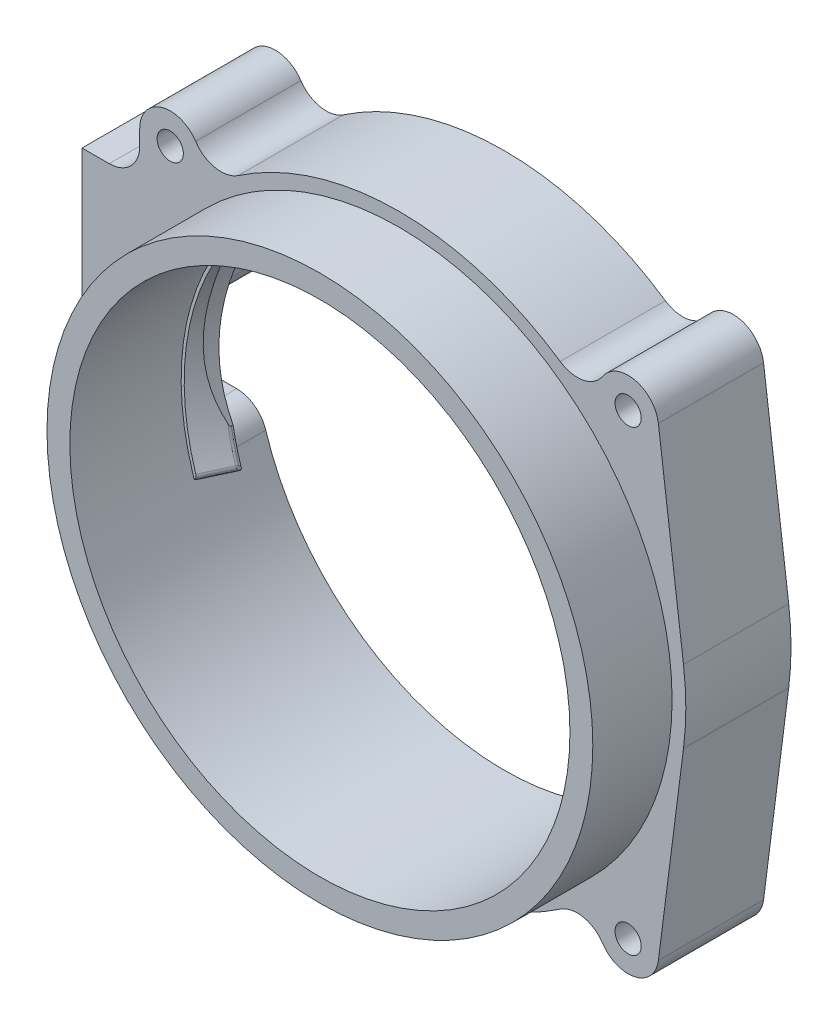
SolidWorks part; units mm, degrees
material "ABS"
ref_plane "前视基准面" through (0, 0, 0) normal (0, 0, 1) x (1, 0, 0)
ref_plane "上视基准面" through (0, 0, 0) normal (0, 1, 0) x (1, 0, 0)
ref_plane "右视基准面" through (0, 0, 0) normal (1, 0, 0) x (0, 0, -1)
sketch "草图1" plane through (0, 0, 0) normal (0, 0, 1) x (1, 0, 0)
  line L0 (0, 0) -> (50000, 0) construction
  line L1 (-52, 8.75) -> (-52, -8.75) construction
  line L2 (-52, 8.75) -> (-52, 30)
  line L3 (-52, -8.75) -> (-52, -30)
  line L4 (-52, 8.75) -> (-43.8969, 8.75)
  line L5 (-52, -8.75) -> (-43.8969, -8.75)
  line L6 (-42.54, 37.5) -> (-42.54, 35)
  line L7 (-47.54, 30) -> (-52, 30)
  line L8 (-47.54, -30) -> (-52, -30)
  line L9 (-42.54, -37.5) -> (-42.54, -35)
  line L10 (0, 0) -> (0, -50000) construction
  line L11 (42.4995, 38.1352) -> (46.6192, 5.9711)
  line L12 (42.4995, -38.1352) -> (46.6192, -5.9711)
  arc A0 (-39.1255, -12.2554) -> (-39.1255, 12.2554) centre (0, 0) ccw
  arc A1 (-40.0554, 8.75) -> (-40.0554, -8.75) centre (0, 0) ccw construction
  circle A2 centre (-37.54, 37.5) radius 2.15
  circle A3 centre (-37.54, -37.5) radius 2.15
  arc A4 (-33.3722, 40.2622) -> (-42.54, 37.5) centre (-37.54, 37.5) ccw
  arc A5 (-42.54, -37.5) -> (-33.3722, -40.2622) centre (-37.54, -37.5) ccw
  arc A6 (-26.3963, -38.8874) -> (26.3963, -38.8874) centre (0, 0) ccw
  arc A7 (-33.3722, 40.2622) -> (-26.3963, 38.8874) centre (-29.2045, 43.0244) ccw
  arc A8 (-33.3722, -40.2622) -> (-42.54, -37.5) centre (-37.54, -37.5) cw
  arc A9 (-33.3722, -40.2622) -> (-26.3963, -38.8874) centre (-29.2045, -43.0244) cw
  circle A10 centre (37.54, -37.5) radius 2.15
  circle A11 centre (37.54, 37.5) radius 2.15
  arc A12 (42.4995, 38.1352) -> (33.3722, 40.2622) centre (37.54, 37.5) ccw
  arc A13 (33.3722, -40.2622) -> (42.4995, -38.1352) centre (37.54, -37.5) ccw
  arc A14 (33.3722, 40.2622) -> (26.3963, 38.8874) centre (29.2045, 43.0244) cw
  arc A15 (33.3722, -40.2622) -> (26.3963, -38.8874) centre (29.2045, -43.0244) ccw
  arc A16 (26.3963, 38.8874) -> (-26.3963, 38.8874) centre (0, 0) ccw
  arc A17 (46.6192, -5.9711) -> (46.6192, 5.9711) centre (0, 0) ccw
  arc A18 (-47.54, -30) -> (-42.54, -35) centre (-47.54, -35) cw
  arc A19 (-42.54, 35) -> (-47.54, 30) centre (-47.54, 35) cw
  arc A20 (-43.8969, 8.75) -> (-39.1255, 12.2554) centre (-43.8969, 13.75) ccw
  arc A21 (-43.8969, -8.75) -> (-39.1255, -12.2554) centre (-43.8969, -13.75) cw
  point P8 (-52, 0)
  point P44 (-42.54, -30)
  point P47 (-42.54, 30)
  dimension "D1" = 82
  dimension "D5" = 4.3
  dimension "D6" = 75
  dimension "D8" = 10
  dimension "D9" = 94
  dimension "D10" = 5
  dimension "D11" = 10
  dimension "D12" = 5
  dimension "D13" = 5
  dimension "D14" = 5
  dimension "D15" = 5
  dimension "D2" = 17.5
  dimension "D3" = 52
  dimension "D4" = 60
  dimension "D7" = 14.46
extrude "凸台-拉伸1" add sketch "草图1" along normal blind 22.5 contours A21 L5 L3 L8 A18 L9 A5 A9 A6 A15 A13 L12 A17 L11 A12 A14 A16 A7 A4 L6 A19 L7 L2 L4 A20 A0 A10 A3 A2 A11 region at (-50.6348, 19.375, 0)
sketch "草图3" plane through (0, 0, 22.5) normal (0, 0, 1) x (1, 0, 0)
  line L0 (-52, -8.75) -> (-43.8969, -8.75) construction
  line L1 (-52, 8.75) -> (-43.8969, 8.75) construction
  line L2 (-52, -8.75) -> (-43.8969, -8.75)
  line L3 (-52, 8.75) -> (-43.8969, 8.75)
  line L4 (-52, 8.75) -> (-52, -8.75)
  arc A1 (-39.1255, -12.2554) -> (-43.8969, -8.75) centre (-43.8969, -13.75) ccw construction
  arc A2 (-43.8969, 8.75) -> (-39.1255, 12.2554) centre (-43.8969, 13.75) ccw construction
  arc A3 (-39.1255, -12.2554) -> (-43.8969, -8.75) centre (-43.8969, -13.75) ccw
  arc A4 (-43.8969, 8.75) -> (-39.1255, 12.2554) centre (-43.8969, 13.75) ccw
  arc A5 (-39.1255, 12.2554) -> (-39.1255, -12.2554) centre (0, 0) ccw
  arc A6 (-39.1255, -12.2554) -> (-39.1255, 12.2554) centre (0, 0) ccw construction
extrude "凸台-拉伸2" add sketch "草图3" against normal blind 14.5
sketch "草图4" plane through (-52, 0, 0) normal (-1, 0, 0) x (0, 0, 1)
  line L0 (0, 0) -> (-50000, 0) construction
  line L1 (22.5, 30) -> (22.5, -30) construction
  line L2 (22.5, 15) -> (8, 15)
  line L3 (22.5, 15) -> (22.5, 13.2)
  line L4 (22.5, 13.2) -> (8, 13.2)
  line L5 (8, 15) -> (8, 13.2)
  line L7 (22.5, -15) -> (8, -15)
  line L8 (22.5, -15) -> (22.5, -13.2)
  line L9 (22.5, -13.2) -> (8, -13.2)
  line L10 (8, -15) -> (8, -13.2)
  dimension "D1" = 26.4
  dimension "D2" = 14.5
  dimension "D3" = 1.8
extrude "凸台-拉伸3" [suppressed] add sketch "草图4" along normal blind 1.2
sketch "草图5" plane through (0, 0, 22.5) normal (0, 0, 1) x (1, 0, 0)
  circle A0 centre (0, 0) radius 44.75
  circle A1 centre (0, 0) radius 41
  dimension "D1" = 89.5
  dimension "D2" = 82
extrude "凸台-拉伸4" add sketch "草图5" along normal blind 11.22
sketch "草图6" plane through (0, 0, 8) normal (0, 0, -1) x (-1, 0, 0)
  line L0 (0, 0) -> (50000, 0) construction
  line L1 (0, 0) -> (0, -50000) construction
  line L2 (0, 0) -> (34.9842, -12.046) construction
  line L3 (34.9842, -12.046) -> (38.7663, -13.3483)
  line L4 (0, 0) -> (27.9243, 24.2742) construction
  line L5 (30.9431, 26.8984) -> (27.9243, 24.2742)
  arc A0 (34.9842, -12.046) -> (27.9243, 24.2742) centre (0, 0) ccw
  arc A1 (39.1255, 12.2554) -> (39.1255, -12.2554) centre (0, 0) ccw construction
  arc A2 (38.7663, -13.3483) -> (30.9431, 26.8984) centre (0, 0) ccw
  dimension "D1" = 37
  dimension "D2" = 19
  dimension "D3" = 41
extrude "凸台-拉伸5" add sketch "草图6" against normal blind 4
chamfer "倒角1" distance 3.5 angle 45 1 edges at (-36.3202, 7.0599, 12)
fillet "圆角1" radius 1 1 edges at (-36.6388, -12.6158, 10.25)
fillet "圆角2" radius 0.5 2 edges at (-35.1439, -11.5717, 8.3208) (-36.2234, 7.541, 8.5)
sketch "草图7" plane through (0, 0, 12) normal (0, 0, 1) x (1, 0, 0)
  line L0 (-38.7663, -13.3483) -> (-35.8361, -12.3394) construction
  line L1 (-30.9431, 26.8984) -> (-27.9243, 24.2742)
  arc A0 (-27.9243, 24.2742) -> (-35.2902, -11.1176) centre (0, 0) ccw construction
  arc A1 (-27.9243, 24.2742) -> (-36.4745, -6.2135) centre (0, 0) ccw
  spline S0 degree 3 poles (-36.4745, -6.2135) (-42.0845, 4.603) (-36.5338, 17.4065) (-30.9431, 26.8984) knots 0 0 0 0 1 1 1 1
  dimension "D1" = 6
extrude "切除-拉伸1" cut sketch "草图7" against normal blind 4
sketch "草图8" plane through (0, 0, 22.5) normal (0, 0, 1) x (1, 0, 0)
  line L7 (-47.54, 30) -> (-52, 30)
  line L8 (-52, 30) -> (-52, -30)
  line L9 (-52, -30) -> (-47.54, -30)
  line L10 (-42.54, -35) -> (-42.54, -37.5)
  line L11 (42.4995, -38.1352) -> (46.6192, -5.9711)
  line L12 (46.6192, 5.9711) -> (42.4995, 38.1352)
  line L13 (-42.54, 37.5) -> (-42.54, 35)
  line L14 (-47.54, 30) -> (-52, 30)
  line L15 (-52, 30) -> (-52, -30)
  line L16 (-52, -30) -> (-47.54, -30)
  line L17 (-42.54, -35) -> (-42.54, -37.5)
  line L18 (42.4995, -38.1352) -> (46.6192, -5.9711)
  line L19 (46.6192, 5.9711) -> (42.4995, 38.1352)
  line L20 (-42.54, 37.5) -> (-42.54, 35)
  circle A0 centre (0, 0) radius 44.75
  circle A1 centre (0, 0) radius 44.75 construction
  arc A13 (-42.54, -35) -> (-47.54, -30) centre (-47.54, -35) ccw
  arc A14 (-42.54, -37.5) -> (-33.3722, -40.2622) centre (-37.54, -37.5) ccw
  arc A15 (-26.3963, -38.8874) -> (-33.3722, -40.2622) centre (-29.2045, -43.0244) ccw
  arc A16 (-26.3963, -38.8874) -> (26.3963, -38.8874) centre (0, 0) ccw
  arc A17 (33.3722, -40.2622) -> (26.3963, -38.8874) centre (29.2045, -43.0244) ccw
  arc A18 (33.3722, -40.2622) -> (42.4995, -38.1352) centre (37.54, -37.5) ccw
  arc A19 (46.6192, -5.9711) -> (46.6192, 5.9711) centre (0, 0) ccw
  arc A20 (42.4995, 38.1352) -> (33.3722, 40.2622) centre (37.54, 37.5) ccw
  arc A21 (26.3963, 38.8874) -> (33.3722, 40.2622) centre (29.2045, 43.0244) ccw
  arc A22 (26.3963, 38.8874) -> (-26.3963, 38.8874) centre (0, 0) ccw
  arc A23 (-33.3722, 40.2622) -> (-26.3963, 38.8874) centre (-29.2045, 43.0244) ccw
  arc A24 (-33.3722, 40.2622) -> (-42.54, 37.5) centre (-37.54, 37.5) ccw
  arc A25 (-47.54, 30) -> (-42.54, 35) centre (-47.54, 35) ccw
  arc A26 (-42.54, -35) -> (-47.54, -30) centre (-47.54, -35) ccw
  arc A27 (-42.54, -37.5) -> (-33.3722, -40.2622) centre (-37.54, -37.5) ccw
  arc A28 (-26.3963, -38.8874) -> (-33.3722, -40.2622) centre (-29.2045, -43.0244) ccw
  arc A29 (-26.3963, -38.8874) -> (26.3963, -38.8874) centre (0, 0) ccw
  arc A30 (33.3722, -40.2622) -> (26.3963, -38.8874) centre (29.2045, -43.0244) ccw
  arc A31 (33.3722, -40.2622) -> (42.4995, -38.1352) centre (37.54, -37.5) ccw
  arc A32 (46.6192, -5.9711) -> (46.6192, 5.9711) centre (0, 0) ccw
  arc A33 (42.4995, 38.1352) -> (33.3722, 40.2622) centre (37.54, 37.5) ccw
  arc A34 (26.3963, 38.8874) -> (33.3722, 40.2622) centre (29.2045, 43.0244) ccw
  arc A35 (26.3963, 38.8874) -> (-26.3963, 38.8874) centre (0, 0) ccw
  arc A36 (-33.3722, 40.2622) -> (-26.3963, 38.8874) centre (-29.2045, 43.0244) ccw
  arc A37 (-33.3722, 40.2622) -> (-42.54, 37.5) centre (-37.54, 37.5) ccw
  arc A38 (-47.54, 30) -> (-42.54, 35) centre (-47.54, 35) ccw
  dimension "D1" = 0
extrude "切除-拉伸2" cut sketch "草图8" against normal blind 5.25
sketch "草图9" plane through (0, 0, 33.72) normal (0, 0, 1) x (1, 0, 0)
  circle A1 centre (0, 0) radius 44.75
  circle A2 centre (0, 0) radius 44.75
  dimension "D1" = 0
extrude "切除-拉伸3" cut sketch "草图9" against normal blind 3.47
